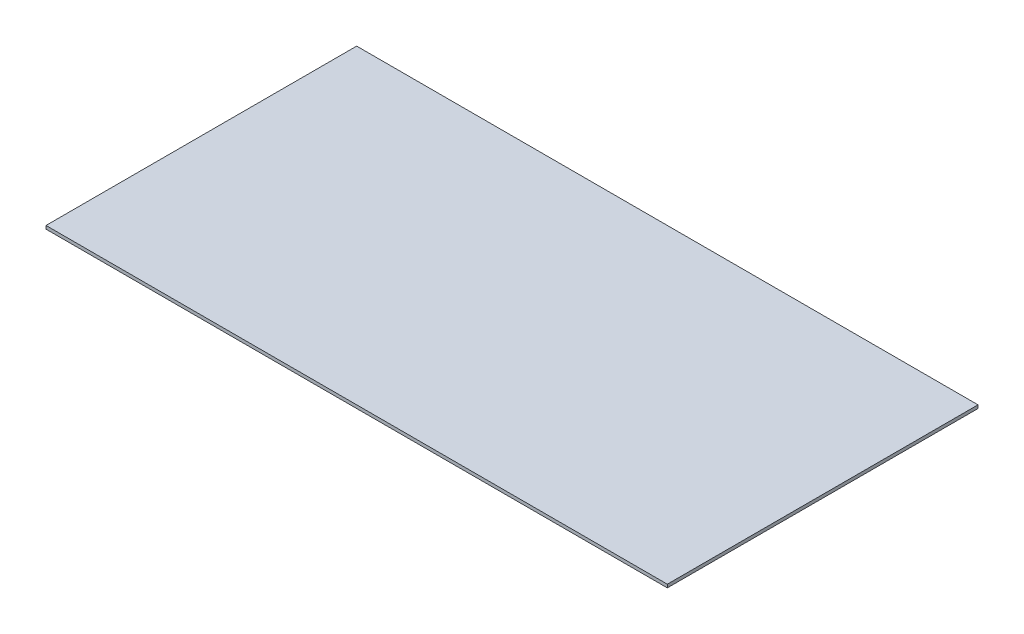
SolidWorks part; units mm, degrees
material "Acrylic (Medium-high impact)"
ref_plane "Front Plane" through (0, 0, 0) normal (0, 0, 1) x (1, 0, 0)
ref_plane "Top Plane" through (0, 0, 0) normal (0, 1, 0) x (1, 0, 0)
ref_plane "Right Plane" through (0, 0, 0) normal (1, 0, 0) x (0, 0, -1)
sketch "Sketch1" plane through (0, 0, 0) normal (0, 1, 0) x (1, 0, 0)
  line L1 (-304.8, -152.4) -> (304.8, -152.4)
  line L2 (-304.8, -152.4) -> (-304.8, 152.4)
  line L3 (-304.8, 152.4) -> (304.8, 152.4)
  line L4 (304.8, -152.4) -> (304.8, 152.4)
  line L5 (-304.8, -152.4) -> (304.8, 152.4) construction
  line L6 (-304.8, 152.4) -> (304.8, -152.4) construction
  point P0 (0, 0)
  dimension "D1" = 609.6
  dimension "D2" = 304.8
extrude "Boss-Extrude1" add sketch "Sketch1" along normal mid plane 3.175
sketch "Sketch2" plane through (0, 1.5875, 0) normal (0, 1, 0) x (1, 0, 0)
  line L0 (304.8, -152.4) -> (304.8, 152.4) construction
  line L1 (-304.8, -152.4) -> (304.8, -152.4) construction
  line L2 (304.8, 152.4) -> (-304.8, 152.4) construction
  line L3 (-304.8, 152.4) -> (-304.8, -152.4) construction
  line L4 (304.8, -152.4) -> (304.8, 152.4) construction
  line L5 (-304.8, -152.4) -> (304.8, -152.4) construction
  line L6 (304.8, 152.4) -> (-304.8, 152.4) construction
  line L7 (-304.8, 152.4) -> (-304.8, -152.4) construction
  line L8 (-304.8, 152.4) -> (-304.8, -152.4)
  line L9 (-304.8, -152.4) -> (-152.4, -152.4)
  line L10 (-152.4, -152.4) -> (-152.4, 152.4)
  line L11 (-152.4, 152.4) -> (-304.8, 152.4)
  dimension "D1" = 152.4
extrude "Cut-Extrude1" [suppressed] cut sketch "Sketch2" against normal through all both and the other way through all
